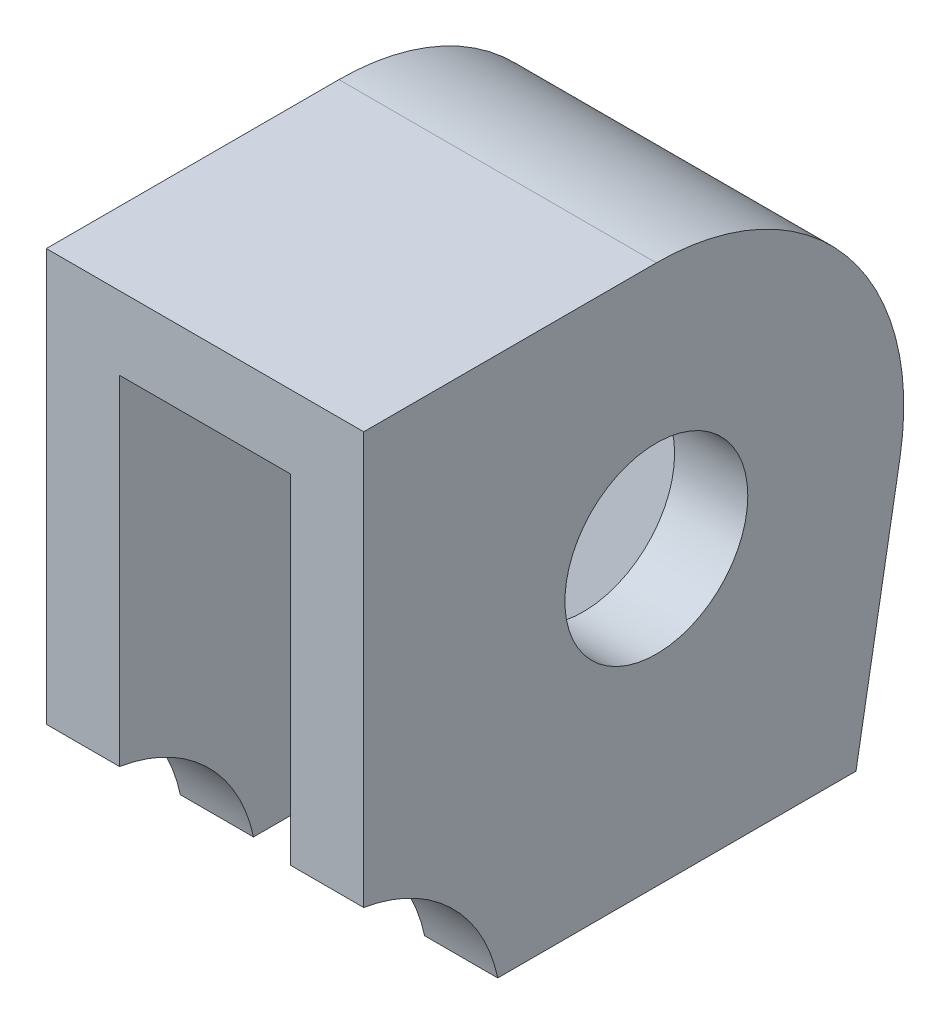
SolidWorks part; units mm, degrees
ref_plane "Front Plane" through (0, 0, 0) normal (0, 0, 1) x (1, 0, 0)
ref_plane "Top Plane" through (0, 0, 0) normal (0, 1, 0) x (1, 0, 0)
ref_plane "Right Plane" through (0, 0, 0) normal (1, 0, 0) x (0, 0, -1)
sketch "Sketch1" plane through (0, 0, 0) normal (1, 0, 0) x (0, 0, -1)
  line L0 (-8, -4.5) -> (-8, 6.7646)
  line L1 (-4.3357, -8) -> (5.4584, -8)
  line L2 (0, 0) -> (-8, 0) construction
  line L3 (0, -7) -> (0, -8) construction
  line L4 (0, 0) -> (0, 6.7646) construction
  line L5 (-8, 6.7646) -> (0, 6.7646)
  line L6 (5.4584, -8) -> (6.6619, -1.1747)
  line L7 (-5.6284, -5.6852) -> (-4.9248, -4.9746) construction
  circle A0 centre (0, 0) radius 7 construction
  arc A1 (-8, -4.5) -> (-4.3357, -8) centre (-8.7365, -8.9393) cw
  arc A2 (0, 6.7646) -> (6.6619, -1.1747) centre (0, 0) cw
  circle A3 centre (0, 0) radius 10 construction
  dimension "D1" = 14
  dimension "D4" = 20
  dimension "D7" = 4.5
  dimension "D2" = 1
  dimension "D3" = 8
  dimension "D6" = 4.5
  dimension "D8" = 100
  dimension "D9" = 1
  dimension "D5" = 6.7646
extrude "Boss-Extrude1" add sketch "Sketch1" along normal blind 2
sketch "Sketch6" plane through (0, 0, 0) normal (-1, 0, 0) x (0, 0, 1)
  line L0 (8, 4.7646) -> (0, 4.7646)
  line L1 (8, 6.7646) -> (8, -4.5) construction
  line L2 (-3.4275, -8) -> (-4.6922, -0.8274)
  line L3 (4.3357, -8) -> (-5.4584, -8) construction
  line L4 (-5.4584, -8) -> (-6.6619, -1.1747) construction
  line L7 (0, 6.7646) -> (8, 6.7646) construction
  line L8 (-3.4275, -8) -> (-5.4584, -8)
  line L9 (-5.4584, -8) -> (-6.6619, -1.1747)
  line L10 (8, 4.7646) -> (8, 6.7646)
  line L11 (8, 6.7646) -> (0, 6.7646)
  arc A0 (0, 4.7646) -> (-4.6922, -0.8274) centre (0, 0) ccw
  arc A1 (0, 6.7646) -> (-6.6619, -1.1747) centre (0, 0) ccw
  dimension "D1" = 2
  dimension "D2" = 2
extrude "Boss-Extrude2" add sketch "Sketch6" along normal blind 2.3388
mirror "Mirror1" about plane through (-2.3388, 0, 0) normal (-1, 0, 0) of bodies 106
sketch "Sketch4" plane through (2, 0, 0) normal (1, 0, 0) x (0, 0, -1)
  circle A0 centre (0, 0) radius 2.5
  dimension "D1" = 5
extrude "Cut-Extrude5" cut sketch "Sketch4" against normal blind 13
equation "\"LA_height\"=6.76462661"
equation "\"partial_pulley_height\"= \"LA_height\""
equation "\"D5@Sketch1\"=\"partial_pulley_height\""
equation "\"LA_width\"=4.67766733"
equation "\"pulley_width\"= \"LA_width\" / 2"
equation "\"D1@Boss-Extrude2\"=\"pulley_width\""
equation "\"LA_length\"=50.00000000"
equation "\"radius_pin\"=2.33883367"
